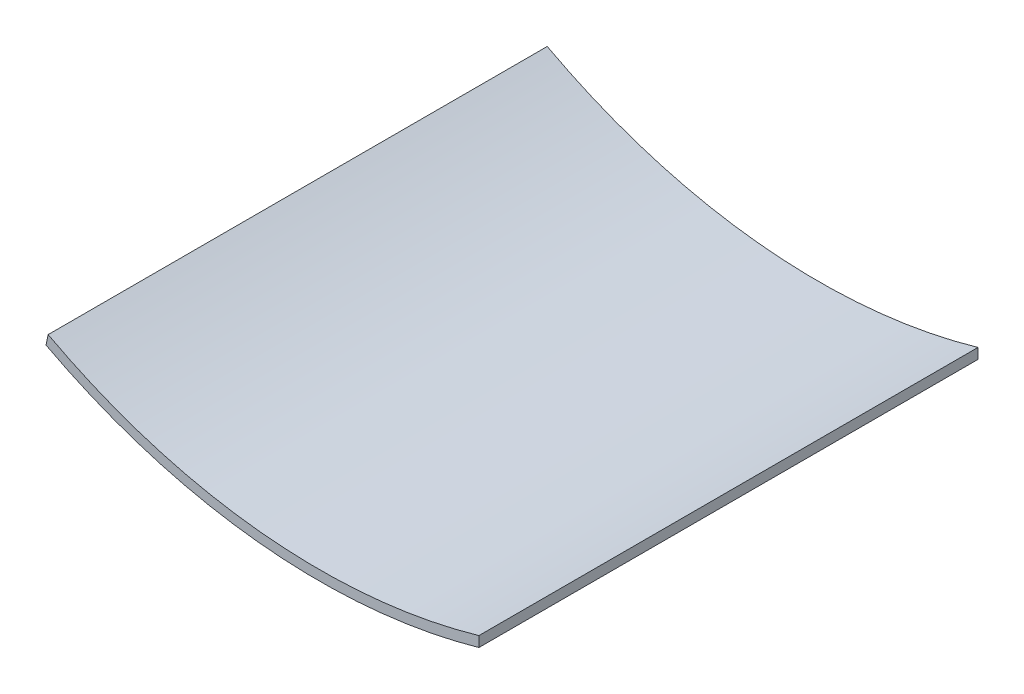
SolidWorks part; units mm, degrees
ref_plane "Front Plane" through (0, 0, 0) normal (1, 0, 0) x (0, 1, 0)
ref_plane "Top Plane" through (0, 0, 0) normal (0, 0, 1) x (0, 1, 0)
ref_plane "Right Plane" through (0, 0, 0) normal (0, 1, 0) x (-1, 0, 0)
sketch "Sketch1" plane through (0, 0, 0) normal (0, 0, 1) x (0, 1, 0)
  line L0 (0, -50.8) -> (-178.9855, -50.8) construction
  line L1 (0, 0) -> (10.5619, 49.6899) construction
  line L2 (0, 0) -> (-175.0743, 37.2132) construction
  line L3 (10.5619, 49.6899) -> (-164.5124, 86.9031) construction
  line L4 (-175.0743, 37.2132) -> (-164.5124, 86.9031) construction
  line L5 (-164.5124, 86.9031) -> (-161.2818, 86.2164)
  line L6 (-178.9855, -50.8) -> (-175.6828, -50.8)
  circle A0 centre (0, 0) radius 50.8 construction
  circle A1 centre (0, 0) radius 182.88 construction
  circle A2 centre (0, 0) radius 186.055 construction
  arc A3 (-161.2818, 86.2164) -> (-175.6828, -50.8) centre (0, 0) ccw
  arc A4 (-164.5124, 86.9031) -> (-178.9855, -50.8) centre (0, 0) ccw
  dimension "D1" = 101.6
  dimension "D2" = 132.08
  dimension "D3" = 3.175
  dimension "D4" = 12
extrude "Boss-Extrude1" add sketch "Sketch1" along normal blind 158.75
